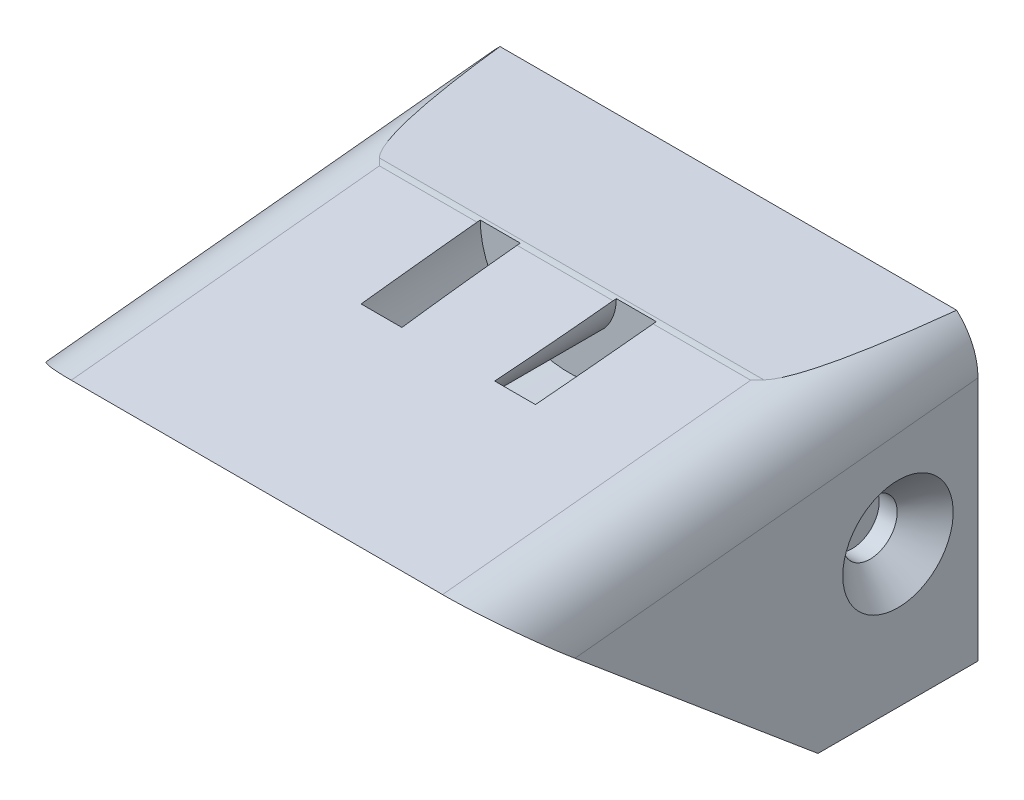
SolidWorks part; units mm, degrees
ref_plane "Front Plane" through (0, 0, 0) normal (0, 0, 1) x (1, 0, 0)
ref_plane "Top Plane" through (0, 0, 0) normal (0, 1, 0) x (1, 0, 0)
ref_plane "Right Plane" through (0, 0, 0) normal (1, 0, 0) x (0, 0, -1)
sketch "Sketch2" plane through (0, 0, 32.3234) normal (0, 0, 1) x (1, 0, 0)
  line L0 (-12.6, 3) -> (-12.6, -11) construction
  line L1 (-15.6, 5.4859) -> (15.6, 5.4859)
  line L2 (-15.6, 5.4859) -> (-15.6, -12.8362)
  line L3 (-15.6, -12.8362) -> (15.6, -12.8362)
  line L4 (15.6, 5.4859) -> (15.6, -12.8362)
  line L5 (12.6, 3) -> (12.6, -11) construction
  dimension "D1" = 3
  dimension "D2" = 3
  dimension "D3" = 31.2
ref_plane "Plane2" through (15.6, 0, 0) normal (-1, 0, 0) x (0, -1, 0)
sketch "Sketch4" plane through (15.6, 0, 0) normal (-1, 0, 0) x (0, -1, 0)
  line L0 (12.8362, 32.3234) -> (-3.4906, 51.7809)
  line L1 (-5.4859, 32.3234) -> (12.8362, 32.3234) construction
  line L3 (-3.4906, 51.7809) -> (-5.4859, 32.3234)
  line L5 (-5.4859, 32.3234) -> (12.8362, 32.3234)
  dimension "D1" = 50
  dimension "D2" = 25.4
extrude "Boss-Extrude1" add sketch "Sketch4" along normal up to vertex (31.2 mm away) up to point (-15.6, -12.8362, 32.3234)
sketch "Sketch5" plane through (0, 0, 32.3234) normal (0, 0, -1) x (-1, 0, 0)
  line L0 (-12.6, -11) -> (-9.6, -11) construction
  line L1 (12.6, -11) -> (9.6, -11) construction
  line L2 (9.6, 3) -> (9.6, -11) construction
  line L3 (-12.6, 3) -> (-12.6, -11) construction
  line L4 (-9.6, 3) -> (-9.6, -11) construction
  line L5 (-12.6, 3) -> (-9.6, 3) construction
  line L6 (12.6, 3) -> (9.6, 3) construction
  line L7 (12.6, 3) -> (12.6, -11) construction
  line L8 (-12.6, -11) -> (-9.6, -11) construction
  line L9 (12.6, -11) -> (9.6, -11) construction
  line L10 (9.6, 3) -> (9.6, -11) construction
  line L11 (-12.6, 3) -> (-12.6, -11) construction
  line L12 (-9.6, 3) -> (-9.6, -11) construction
  line L13 (-12.6, 3) -> (-9.6, 3) construction
  line L14 (12.6, 3) -> (9.6, 3) construction
  line L15 (12.6, 3) -> (12.6, -11) construction
  line L16 (-12.725, -11.125) -> (-9.475, -11.125)
  line L17 (-9.475, 3.125) -> (-9.475, -11.125)
  line L18 (-12.725, 3.125) -> (-9.475, 3.125)
  line L19 (-12.725, 3.125) -> (-12.725, -11.125)
  line L20 (12.725, -11.125) -> (9.475, -11.125)
  line L21 (9.475, 3.125) -> (9.475, -11.125)
  line L22 (12.725, 3.125) -> (9.475, 3.125)
  line L23 (12.725, 3.125) -> (12.725, -11.125)
  line L24 (-15.6, 5.4859) -> (-15.6, -12.8362) construction
  line L25 (15.6, -12.8362) -> (-15.6, -12.8362) construction
  line L26 (15.6, 5.4859) -> (15.6, -12.8362) construction
  line L27 (15.6, 5.4859) -> (-15.6, 5.4859) construction
  line L28 (-15.6, 5.4859) -> (-15.6, -12.8362)
  line L29 (15.6, -12.8362) -> (-15.6, -12.8362)
  line L30 (15.6, 5.4859) -> (15.6, -12.8362)
  line L31 (15.6, 5.4859) -> (-15.6, 5.4859)
  dimension "D1" = 0.125
extrude "Boss-Extrude2" add sketch "Sketch5" along normal up to vertex (10 mm away)
sketch "Sketch6" plane through (15.6, 0, 0) normal (1, 0, 0) x (0, 0, -1)
  circle A0 centre (-27.3234, -4) radius 1.75 construction
  circle A1 centre (-27.3234, -4) radius 1.7
  circle A2 centre (-27.3234, -4) radius 1.75 construction
  dimension "D1" = 3.4
extrude "Cut-Extrude1" cut sketch "Sketch6" against normal up to vertex
sketch "Sketch8" plane through (9.475, 0, 0) normal (1, 0, 0) x (0, 0, -1)
  line L0 (-32.3234, -11.125) -> (-32.3234, 3.125) construction
  line L1 (-32.3234, -11.125) -> (-32.3234, 3.125)
  line L2 (-32.3234, -11.125) -> (-39.4484, -4)
  line L3 (-39.4484, -4) -> (-32.3234, 3.125)
  point P2 (-32.3234, -4)
  dimension "D1" = 45
extrude "Cut-Extrude2" cut sketch "Sketch8" along normal up to vertex (3.25 mm away)
chamfer "Chamfer1" distance 1.75 angle 45 2 edges at (-15.6, -4, 25.6234) (15.6, -4, 25.6234)
mirror "Mirror1" about plane through (0, 0, 0) normal (1, 0, 0) of "Cut-Extrude2"
fillet "Fillet2" radius 4 3 edges at (-15.6, 4.4883, 42.0521) (0, 5.4859, 32.3234) (15.6, 4.4883, 42.0521)
ref_plane "Plane3" through (0, 0, 32.3234) normal (0, 0, 1) x (1, 0, 0)
sketch "Sketch9" plane through (0, 0, 32.3234) normal (0, 0, 1) x (1, 0, 0)
  line L0 (-12.008, 5.4859) -> (12.008, 5.4859) construction
  line L1 (-12.008, 5.4859) -> (12.008, 5.4859) construction
  line L2 (3, 5.4859) -> (5.5, 5.4859)
  line L3 (-5.5, 5.4859) -> (-3, 5.4859)
  arc A0 (-5.5, 5.4859) -> (5.5, 5.4859) centre (0, 5.4859) ccw
  arc A1 (-3, 5.4859) -> (3, 5.4859) centre (0, 5.4859) ccw
  dimension "D1" = 2.5
  dimension "D2" = 3
extrude "Cut-Extrude3" cut sketch "Sketch9" along normal blind 7.5
